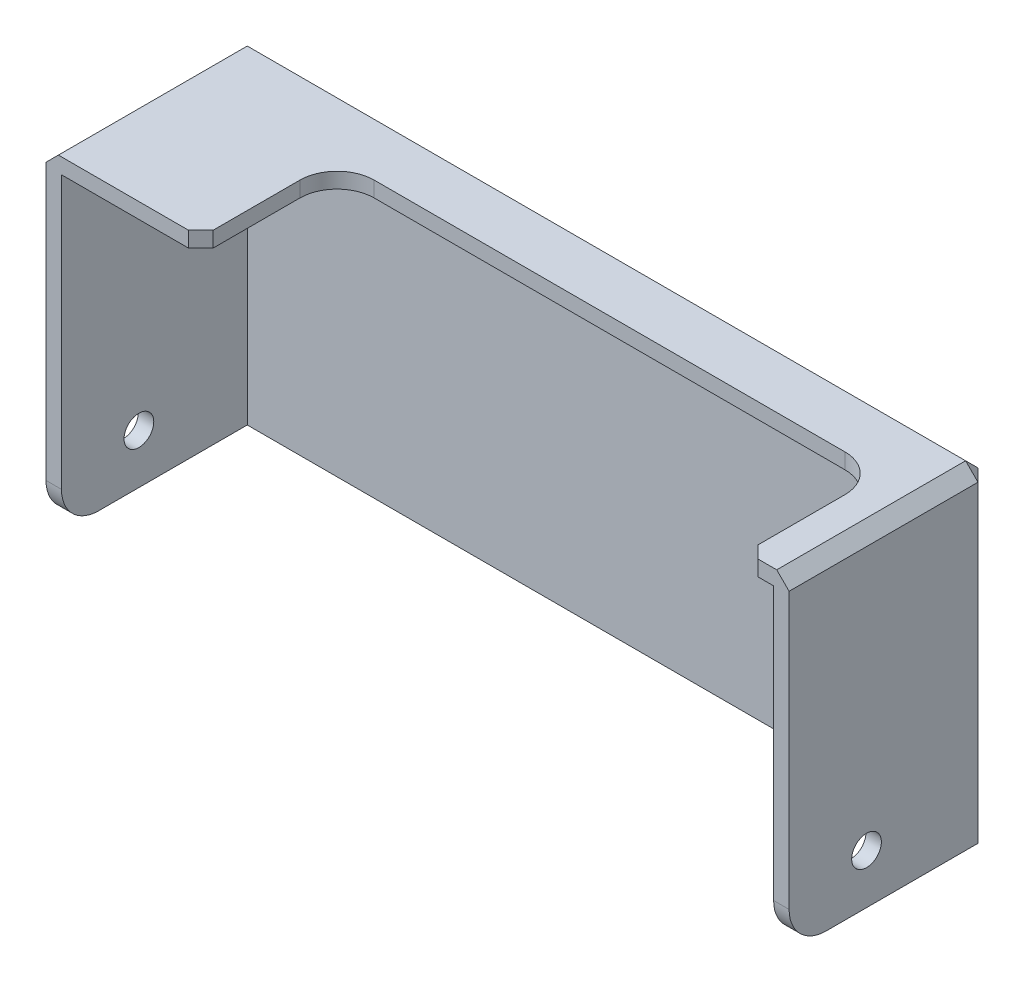
SolidWorks part; units mm, degrees
ref_plane "Front Plane" through (0, 0, 0) normal (0, 0, 1) x (1, 0, 0)
ref_plane "Top Plane" through (0, 0, 0) normal (0, 1, 0) x (1, 0, 0)
ref_plane "Right Plane" through (0, 0, 0) normal (1, 0, 0) x (0, 0, -1)
sketch "Sketch1" plane through (0, 0, 0) normal (0, 0, 1) x (1, 0, 0)
  line L1 (-57.5, -25) -> (57.5, -25)
  line L2 (-57.5, -25) -> (-57.5, 25)
  line L3 (-57.5, 25) -> (57.5, 25)
  line L4 (57.5, -25) -> (57.5, 25)
  line L5 (-57.5, -25) -> (57.5, 25) construction
  line L6 (-57.5, 25) -> (57.5, -25) construction
  point P0 (0, 0)
  dimension "D1" = 50
  dimension "D2" = 115
extrude "Boss-Extrude1" add sketch "Sketch1" along normal blind 30
sketch "Sketch2" plane through (0, 25, 0) normal (0, 1, 0) x (1, 0, 0)
  line L0 (57.5, -30) -> (-57.5, -30) construction
  line L1 (-35, -30) -> (53, -30)
  line L2 (-35, -30) -> (-35, -8)
  line L3 (-35, -8) -> (53, -8)
  line L4 (53, -30) -> (53, -8)
  line L6 (57.5, -30) -> (57.5, 0) construction
  line L7 (-57.5, -30) -> (-57.5, 0) construction
  dimension "D1" = 22.5
  dimension "D2" = 4.5
  dimension "D3" = 22
extrude "Cut-Extrude1" cut sketch "Sketch2" against normal through all
sketch "Sketch3" plane through (0, 0, 30) normal (0, 0, 1) x (1, 0, 0)
  line L0 (53, -25) -> (57.5, -25) construction
  line L1 (57.25, -25) -> (-57.25, -25)
  line L2 (57.25, -25) -> (57.25, 15)
  line L3 (57.25, 15) -> (-57.25, 15)
  line L4 (-57.25, -25) -> (-57.25, 15)
  line L5 (0, 15) -> (0, -25) construction
  line L7 (57.5, 25) -> (53, 25) construction
  dimension "D1" = 114.5
  dimension "D2" = 10
extrude "Cut-Extrude2" [suppressed] cut sketch "Sketch3" against normal blind 30
shell "Shell1" thickness 2.5 removed face at (-35, 0, 19) removed face at (9, 0, 8) removed face at (53, 0, 19) removed face at (55.25, 0, 30) removed face at (4.5, -25, 17) removed face at (-46.25, 0, 30) outward yes
sketch "Sketch6" plane through (-60, 0, 0) normal (-1, 0, 0) x (0, 0, 1)
  line L0 (0, 25) -> (0, -25) construction
  line L1 (30, 25) -> (0, 25) construction
  point P0 (17.5, -17)
  dimension "D1" = 17.5
  dimension "D2" = 42
hole_wizard "M4 Clearance Hole1" positions "Sketch6" profile "Sketch5" hole size "M4" standard "ISO" end condition through all
sketch "Sketch5" plane through (-60, -17, 17.5) normal (0, 1, 0) x (0, 0, 1)
  line L0 (0, 0) -> (0, 120)
  line L1 (0, 120) -> (2.4, 120)
  line L2 (2.4, 120) -> (2.4, 0)
  line L5 (2.4, 0) -> (0, 0)
  line L11 (0, -6.35) -> (0, 107.95) construction
  dimension "Thru Hole Dia." = 4.8
  dimension "Thru Hole Depth" = 120
chamfer "Chamfer1" distance 2 angle 45 8 edges at (0, 27.5, -2.5) (60, 27.5, 13.75) (60, 1.25, -2.5) (0, -25, -2.5) (-60, 1.25, -2.5) (-60, 27.5, 13.75) (53, 26.25, 30) (-35, 26.25, 30)
fillet "Fillet1" radius 6 2 edges at (-35, 26.25, 8) (53, 26.25, 8)
fillet "Fillet2" radius 6 2 edges at (58.75, -25, 30) (-58.75, -25, 30)
